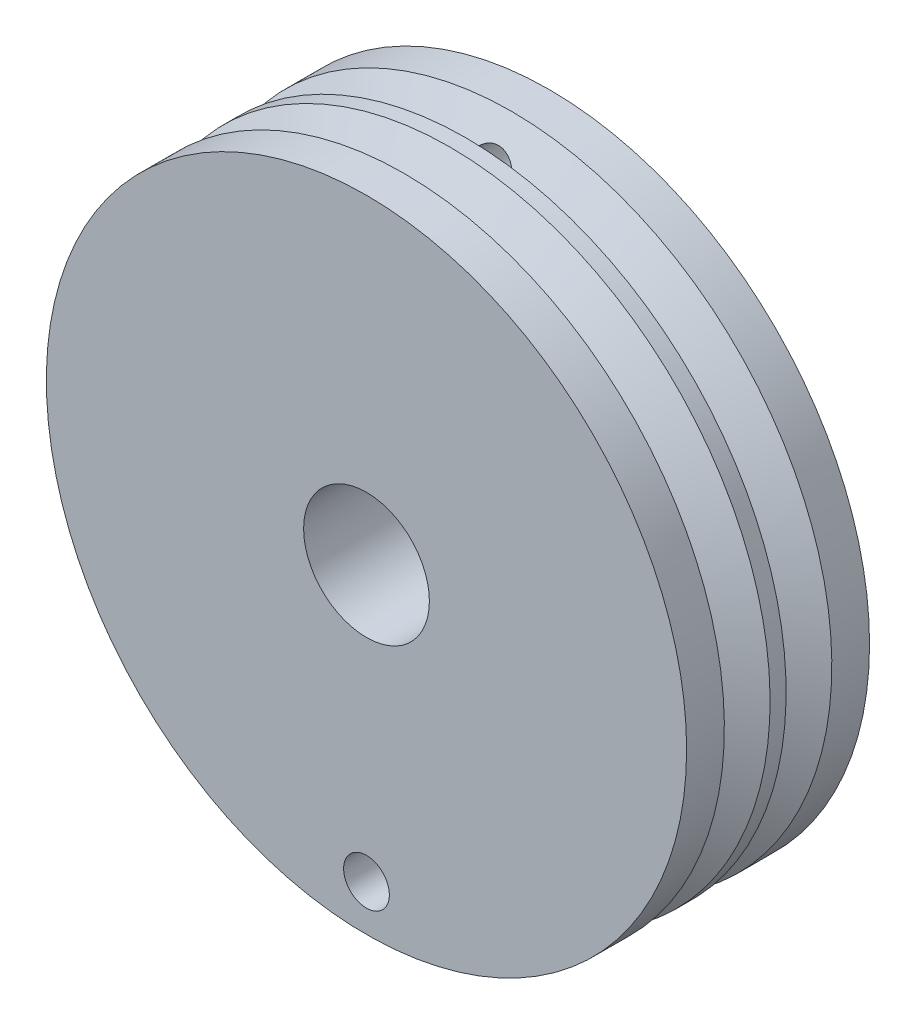
SolidWorks part; units mm, degrees
material "ABS"
ref_plane "Front Plane" through (0, 0, 0) normal (0, 0, 1) x (1, 0, 0)
ref_plane "Top Plane" through (0, 0, 0) normal (0, 1, 0) x (1, 0, 0)
ref_plane "Right Plane" through (0, 0, 0) normal (1, 0, 0) x (0, 0, -1)
sketch "Sketch1" plane through (0, 0, 0) normal (0, 0, 1) x (1, 0, 0)
  circle A0 centre (0, 0) radius 14
  dimension "D1" = 28
extrude "Boss-Extrude1" add sketch "Sketch1" along normal mid plane 8
sketch "Sketch3" plane through (0, 0, 0) normal (1, 0, 0) x (0, 0, -1)
  line L0 (-4, -14) -> (4, -14) construction
  line L1 (0, 0) -> (0, -14) construction
  line L2 (-4, -14) -> (4, -14) construction
  line L3 (2.35, -14) -> (1.35, -12.2679)
  line L4 (1.35, -12.2679) -> (0.35, -14)
  line L5 (0.35, -14) -> (2.35, -14)
  line L6 (4, 0) -> (-4, 0) construction
  line L7 (4, -14) -> (4, 14) construction
  line L8 (-4, 14) -> (-4, -14) construction
  line L9 (-0.35, -14) -> (-2.35, -14)
  line L10 (-2.35, -14) -> (-1.35, -12.2679)
  line L11 (-1.35, -12.2679) -> (-0.35, -14)
  point P18 (0, 0)
  dimension "D1" = 2
  dimension "D2" = 1.35
revolve "Cut-Revolve2" cut sketch "Sketch3" angle 360 about L6
sketch "Sketch11" plane through (0, 0, -4) normal (0, 0, -1) x (-1, 0, 0)
  line L0 (0, 0) -> (0, 14) construction
  circle A0 centre (0, 0) radius 14 construction
  circle A1 centre (0, 12) radius 1
  dimension "D1" = 2
  dimension "D2" = 2
extrude "Cut-Extrude1" cut sketch "Sketch11" against normal up to surface (2.5193 mm away) up to face at (0, 14, -0.35)
sketch "Sketch12" plane through (0, 0, 4) normal (0, 0, 1) x (1, 0, 0)
  line L0 (0, 14) -> (0, -14) construction
  circle A0 centre (0, 0) radius 14 construction
  circle A1 centre (0, -12) radius 1
  dimension "D1" = 2
  dimension "D2" = 2
extrude "Cut-Extrude2" cut sketch "Sketch12" against normal up to surface (5.2193 mm away) up to face at (-0.0394, 0.3645, -1.5605)
sketch "Sketch13" plane through (0, 0, -4) normal (0, 0, -1) x (-1, 0, 0)
  circle A0 centre (0, 0) radius 2.75
  dimension "D1" = 5.5
extrude "Cut-Extrude3" cut sketch "Sketch13" against normal up to surface (8 mm away) up to face at (1, -12, 4)
